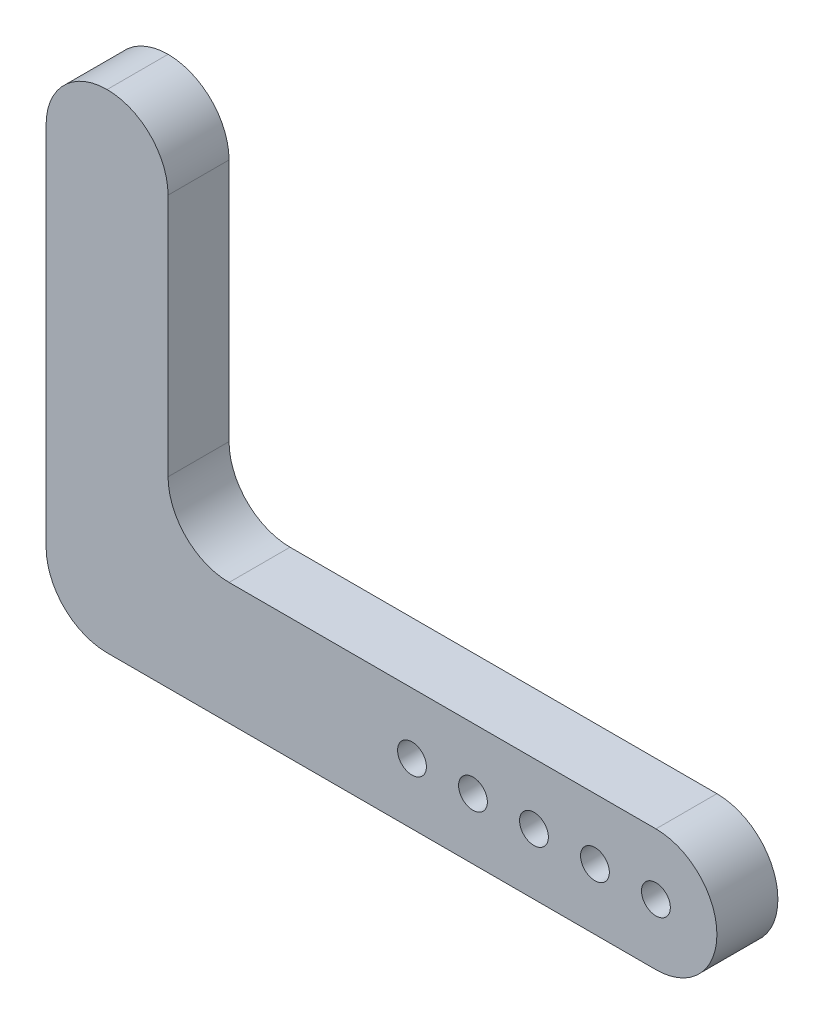
SolidWorks part; units mm, degrees
ref_plane "Front Plane" through (0, 0, 0) normal (0, 0, 1) x (1, 0, 0)
ref_plane "Top Plane" through (0, 0, 0) normal (0, 1, 0) x (1, 0, 0)
ref_plane "Right Plane" through (0, 0, 0) normal (1, 0, 0) x (0, 0, -1)
sketch "Sketch1" plane through (0, 0, 0) normal (0, 0, 1) x (1, 0, 0)
  line L0 (0, 6.35) -> (-50.8, 6.35)
  line L1 (-50.8, 6.35) -> (-50.8, 44.45)
  line L2 (-50.8, 44.45) -> (-63.5, 44.45)
  line L3 (-63.5, 44.45) -> (-63.5, -6.35)
  line L4 (-63.5, -6.35) -> (0, -6.35)
  circle A0 centre (0, 0) radius 1.5
  arc A1 (0, -6.35) -> (0, 6.35) centre (0, 0) ccw
  dimension "D1" = 50.8
  dimension "D2" = 3
  dimension "D5" = 6.35
  dimension "D3" = 63.5
  dimension "D4" = 50.8
extrude "Boss-Extrude1" add sketch "Sketch1" along normal blind 6.35
fillet "Fillet1" radius 6.35 4 edges at (-63.5, -6.35, 3.175) (-50.8, 6.35, 3.175) (-63.5, 44.45, 3.175) (-50.8, 44.45, 3.175)
sketch "Sketch2" plane through (0, 0, 0) normal (0, 0, -1) x (-1, 0, 0)
  line L0 (0, 0) -> (25.4, 0) construction
  circle A0 centre (6.35, 0) radius 1.5
  circle A1 centre (12.7, 0) radius 1.5
  circle A2 centre (25.4, 0) radius 1.5
  circle A3 centre (0, 0) radius 1.5 construction
  circle A4 centre (19.05, 0) radius 1.5
  dimension "D2" = 3
  dimension "D4" = 6.35
  dimension "D5" = 6.35
  dimension "D1" = 25.4
  dimension "D3" = 6.35
extrude "Cut-Extrude1" cut sketch "Sketch2" against normal through all
